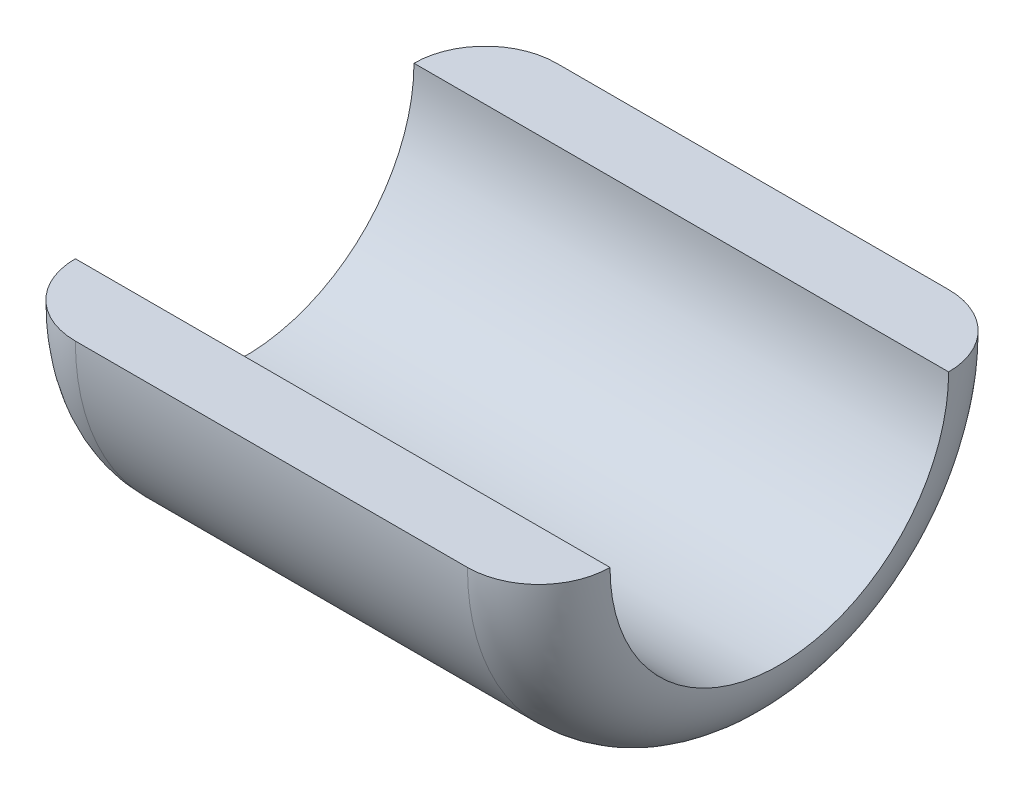
SolidWorks part; units mm, degrees
material "Brass"
ref_plane "Front Plane" through (0, 0, 0) normal (0, 0, 1) x (1, 0, 0)
ref_plane "Top Plane" through (0, 0, 0) normal (0, 1, 0) x (1, 0, 0)
ref_plane "Right Plane" through (0, 0, 0) normal (1, 0, 0) x (0, 0, -1)
sketch "Sketch4" plane through (12, 0, 0) normal (-1, 0, 0) x (0, 0, 1)
  circle A0 centre (0, 0) radius 4.75
  circle A1 centre (0, 0) radius 6.75
  dimension "D1" = 9.5
  dimension "D2" = 13.5
extrude "Boss-Extrude4" add sketch "Sketch4" along normal blind 15 separate body
fillet "Fillet3" radius 2 1 edges at (12, -6.75, 0)
fillet "Fillet4" radius 2 1 edges at (-3, -6.75, 0)
sketch "Sketch5" plane through (0, 0, 0) normal (1, 0, 0) x (0, 0, -1)
  line L0 (-6.75, 0) -> (-4.75, 0)
  line L2 (4.75, 0) -> (6.75, 0)
  circle A0 centre (0, 0) radius 6.75 construction
  circle A1 centre (0, 0) radius 4.75 construction
  circle A2 centre (0, 0) radius 4.75
  circle A3 centre (0, 0) radius 6.75
sketch "Sketch7" plane through (0, 0, 0) normal (1, 0, 0) x (0, 0, -1)
extrude "Cut-Extrude1" cut sketch "Sketch5" along normal through all both and the other way through all contours L2 A3 L0 A2 region at (0, 6.5991, 0)
